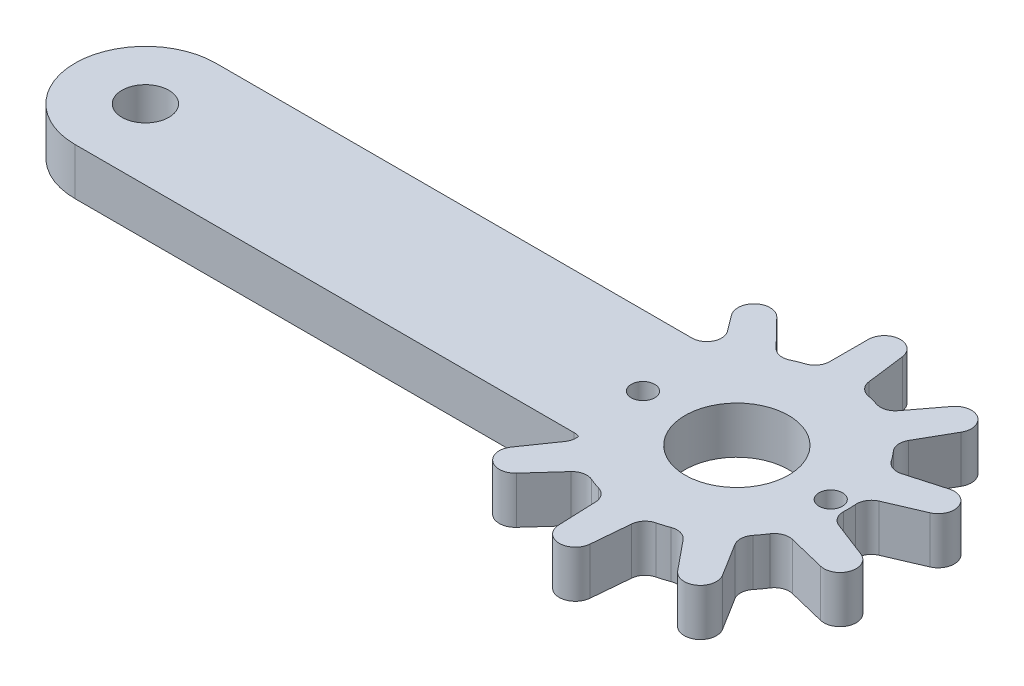
SolidWorks part; units mm, degrees
ref_plane "Alzado" through (0, 0, 0) normal (0, 0, 1) x (1, 0, 0)
ref_plane "Planta" through (0, 0, 0) normal (0, 1, 0) x (1, 0, 0)
ref_plane "Vista lateral" through (0, 0, 0) normal (1, 0, 0) x (0, 0, -1)
sketch "Croquis1" plane through (0, 0, 0) normal (0, 1, 0) x (1, 0, 0)
  line L1 (-20, 0) -> (20, 0)
  line L3 (-20, -9.525) -> (20, -9.525)
  arc A0 (-20, 0) -> (-20, -9.525) centre (-20, -4.7625) ccw
  arc A1 (20, -9.525) -> (20, 0) centre (20, -4.7625) ccw
  circle A2 centre (-20, -4.7625) radius 1.5875
  circle A3 centre (20, -4.7625) radius 1.5875
  dimension "D3" = 4.7625
  dimension "D5" = 3.175
  dimension "D6" = 3.175
  dimension "D1" = 40
  dimension "D2" = 9.525
  dimension "D4" = 40
extrude "Saliente-Extruir1" add sketch "Croquis1" along normal blind 3.175
sketch "Croquis2" plane through (0, 3.175, 0) normal (0, 1, 0) x (1, 0, 0)
  line L0 (20, -1004.7625) -> (20, 48995.2375) construction
  circle A0 centre (20, -4.7625) radius 7.5
  circle A1 centre (20, 14.7375) radius 9 construction
  circle A2 centre (20, -4.7625) radius 1.5875
  dimension "D1" = 15
  dimension "D2" = 18
  dimension "D3" = 19.5
extrude "Saliente-Extruir2" add sketch "Croquis2" against normal blind 3.175
sketch "Croquis7" plane through (0, 3.175, 0) normal (0, 1, 0) x (1, 0, 0)
  circle A0 centre (20, -4.7625) radius 3.5
  circle A1 centre (13.65, -4.7625) radius 0.7937
  circle A2 centre (26.35, -4.7625) radius 0.7937
  dimension "D1" = 7
  dimension "D2" = 1.5875
  dimension "D3" = 1.5875
  dimension "D4" = 6.35
  dimension "D5" = 6.35
extrude "Cortar-Extruir3" cut sketch "Croquis7" against normal blind 10
sketch "Croquis8" plane through (0, 3.175, 0) normal (0, 1, 0) x (1, 0, 0)
  line L0 (20, -4.7625) -> (-29071.9665, 40660.4252) construction
  line L1 (20, -4.7625) -> (-22676.5039, 22236.8096) construction
  line L2 (20, -4.7625) -> (-23649.2675, 19451.2229) construction
  line L3 (20, -4.7625) -> (-25417.0581, 43041.2138) construction
  line L4 (11.6078, 3.4615) -> (14.2062, 0)
  line L6 (13.1634, 4.7938) -> (16.1844, 1.6944)
  arc A1 (16.1844, 1.6944) -> (14.2062, 0) centre (20, -4.7625) ccw
  arc A2 (13.1634, 4.7938) -> (11.6078, 3.4615) centre (20, -4.7625) ccw
  arc A3 (14.2062, -9.525) -> (14.2062, 0) centre (20, -4.7625) ccw construction
  dimension "D1" = 23.5
  dimension "D2" = 5
  dimension "D3" = 10
  dimension "D4" = 5
extrude "Saliente-Extruir3" add sketch "Croquis8" against normal blind 3.175
sketch "Croquis9" plane through (0, 3.175, 0) normal (0, 1, 0) x (1, 0, 0)
  line L0 (16.1844, 1.6944) -> (13.1634, 4.7938) construction
  line L1 (11.6078, 3.4615) -> (14.2062, 0) construction
  line L2 (11.6078, 3.4615) -> (12.194, 2.6806)
  line L3 (13.8449, 4.0946) -> (13.1634, 4.7938)
  arc A0 (13.8449, 4.0946) -> (12.194, 2.6806) centre (13.065, 3.3344) ccw
  arc A1 (13.1634, 4.7938) -> (11.6078, 3.4615) centre (20, -4.7625) ccw construction
  arc A2 (13.1634, 4.7938) -> (11.6078, 3.4615) centre (20, -4.7625) ccw
  line M6 (16.1844, 1.6944) -> (13.1634, 4.7938)
  arc M7 (13.1634, 4.7938) -> (11.6078, 3.4615) centre (20, -4.7625) ccw
  line M8 (11.6078, 3.4615) -> (14.2062, 0)
extrude "Cortar-Extruir4" cut sketch "Croquis9" against normal blind 10 contours A0 M7 M8 | A0 M6 M7
pattern_circular "MatrizC1" count 8 every 37 about axis through (20, 0, 4.7625) along (0, 1, 0) of "Saliente-Extruir3", "Cortar-Extruir4"
fillet "Redondeo1" radius 1 17 edges at (14.2062, 1.5875, 9.525) (14.3898, 1.5875, 9.74) (16.4305, 1.5875, 11.3586) (18.515, 1.5875, 12.114) (21.1189, 1.5875, 12.1786) (23.2383, 1.5875, 11.5274) (25.3567, 1.5875, 10.0118) (26.6574, 1.5875, 8.2163) (27.4372, 1.5875, 5.7311) (27.3954, 1.5875, 3.5143) (26.5225, 1.5875, 1.0602) (20.8386, 1.5875, -2.6905) (22.981, 1.5875, -2.1196) (14.2062, 1.5875, 0) (18.239, 1.5875, -2.5278) (16.1844, 1.5875, -1.6944) (25.1551, 1.5875, -0.685)
